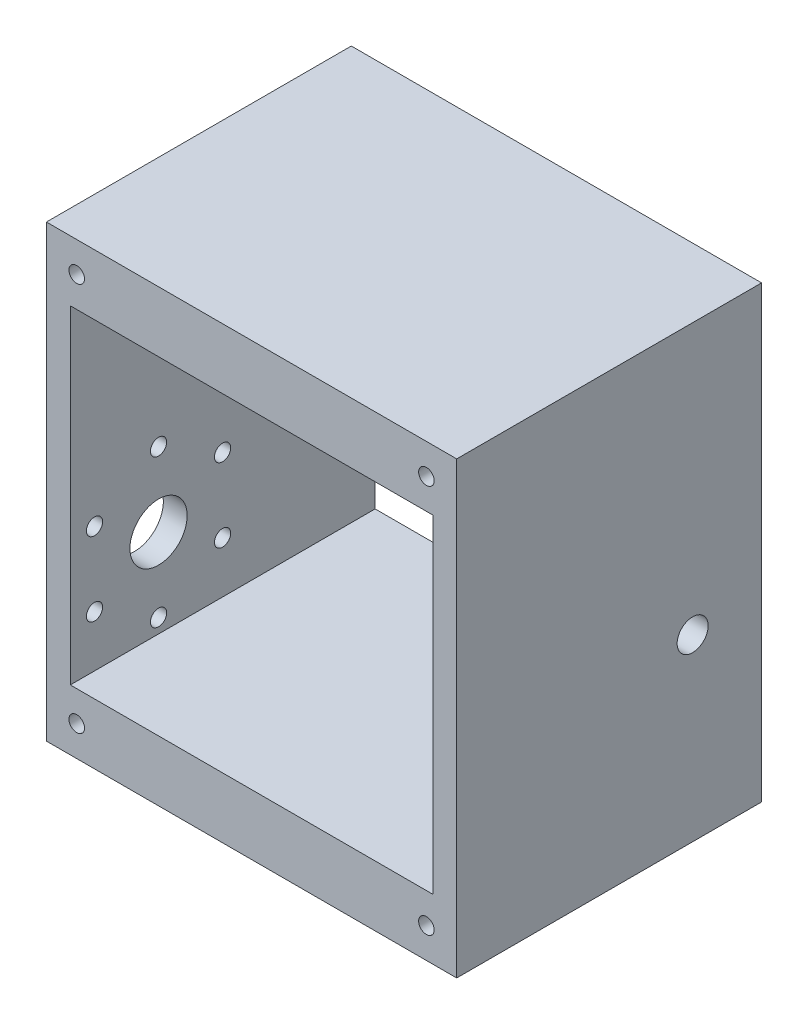
SolidWorks part; units mm, degrees
ref_plane "Front Plane" through (0, 0, 0) normal (0, 0, 1) x (1, 0, 0)
ref_plane "Top Plane" through (0, 0, 0) normal (0, 1, 0) x (1, 0, 0)
ref_plane "Right Plane" through (0, 0, 0) normal (1, 0, 0) x (0, 0, -1)
sketch "Sketch1" plane through (0, 0, 0) normal (0, 0, 1) x (1, 0, 0)
  line L1 (-43, -47.117) -> (43, -47.117)
  line L2 (-43, -47.117) -> (-43, 47.117)
  line L3 (-43, 47.117) -> (43, 47.117)
  line L4 (43, -47.117) -> (43, 47.117)
  line L5 (-43, -47.117) -> (43, 47.117) construction
  line L6 (-43, 47.117) -> (43, -47.117) construction
  point P0 (0, 0)
  dimension "D1" = 86
  dimension "D2" = 94.234
extrude "Boss-Extrude1" add sketch "Sketch1" along normal blind 63.9031
sketch "Sketch2" plane through (0, 0, 63.9031) normal (0, 0, 1) x (1, 0, 0)
  line L0 (-43, 47.117) -> (-43, -47.117) construction
  line L1 (-38, -34.417) -> (38, -34.417)
  line L2 (-38, -34.417) -> (-38, 34.417)
  line L3 (-38, 34.417) -> (38, 34.417)
  line L4 (38, -34.417) -> (38, 34.417)
  line L5 (-38, -34.417) -> (38, 34.417) construction
  line L6 (-38, 34.417) -> (38, -34.417) construction
  line L7 (43, 47.117) -> (-43, 47.117) construction
  point P0 (0, 0)
  dimension "D1" = 5
  dimension "D2" = 12.7
extrude "Cut-Extrude1" cut sketch "Sketch2" against normal through all
hole_wizard "Ø6.5 (6.5) Diameter Hole1" positions "Sketch3" profile "Sketch4" hole size "Ø6.5" standard "ANSI Metric" end condition up to next
sketch "Sketch3" plane through (43, 0, 0) normal (1, 0, 0) x (0, 0, -1)
  line L0 (0, -47.117) -> (0, 47.117) construction
  line L1 (0, 34.417) -> (-63.9031, 34.417) construction
  point P0 (-14.4502, -9.525)
  dimension "D1" = 14.4502
  dimension "D2" = 43.942
sketch "Sketch4" plane through (43, -9.525, 14.4502) normal (0, 1, 0) x (0, 0, -1)
  line L0 (0, 0) -> (0, 5)
  line L1 (0, 5) -> (3.25, 5)
  line L2 (3.25, 5) -> (3.25, 0)
  line L5 (3.25, 0) -> (0, 0)
  line L11 (0, -6.35) -> (0, 107.95) construction
  dimension "Thru Hole Dia." = 6.5
  dimension "Thru Hole Depth" = 5
sketch "Sketch5" plane through (-43, 0, 0) normal (-1, 0, 0) x (0, 0, 1)
  line L0 (63.9031, 47.117) -> (63.9031, -47.117) construction
  line L1 (0, -34.417) -> (63.9031, -34.417) construction
  point P0 (45.4031, -15.917)
  dimension "D1" = 18.5
  dimension "D2" = 18.5
hole_wizard "Ø12.0 (12) Diameter Hole1" positions "Sketch6" profile "Sketch7" hole size "Ø12.0" standard "ANSI Metric" end condition up to next
sketch "Sketch6" plane through (-43, 0, 0) normal (-1, 0, 0) x (0, 0, 1)
  point P0 (45.4031, -15.917)
sketch "Sketch7" plane through (-43, -15.917, 45.4031) normal (0, 1, 0) x (0, 0, 1)
  line L0 (0, 0) -> (0, 5)
  line L1 (0, 5) -> (6, 5)
  line L2 (6, 5) -> (6, 0)
  line L5 (6, 0) -> (0, 0)
  line L11 (0, -6.35) -> (0, 107.95) construction
  dimension "Thru Hole Dia." = 12
  dimension "Thru Hole Depth" = 5
hole_wizard "CSK for M3 Flat Head Machine Screw1" positions "Sketch8" profile "Sketch9" countersink size "M3" standard "ANSI Metric" end condition up to next
sketch "Sketch8" plane through (-43, 0, 0) normal (-1, 0, 0) x (0, 0, 1)
  line L0 (45.4031, -15.917) -> (45.4031, -0.417) construction
  point P0 (45.4031, -0.417)
  point P12 (58.8265, -8.167)
  point P13 (58.8265, -23.667)
  point P14 (45.4031, -31.417)
  point P15 (31.9797, -23.667)
  point P16 (31.9797, -8.167)
  dimension "D2" = 15.5
sketch "Sketch9" plane through (-43, -0.417, 45.4031) normal (0, 1, 0) x (0, 0, 1)
  line L0 (0, 0) -> (0, 5)
  line L1 (0, 5) -> (1.7, 5)
  line L2 (1.7, 5) -> (1.7, 1.45)
  line L3 (1.7, 1.45) -> (3.15, 0)
  line L5 (3.15, 0) -> (0, 0)
  line L6 (-1.7, 1.45) -> (-3.15, 0) construction
  line L11 (0, -6.35) -> (0, 107.95) construction
  dimension "Thru Hole Dia." = 3.4
  dimension "Thru Hole Depth" = 5
  dimension "Near C'Sink Dia." = 6.3
  dimension "Near C'Sink Angle" = 90
hole_wizard "#4 Clearance Hole1" positions "Sketch10" profile "Sketch11" hole size "#4" standard "ANSI Inch" end condition through all
sketch "Sketch10" plane through (0, 0, 63.9031) normal (0, 0, 1) x (1, 0, 0)
  line L0 (-43, 47.117) -> (-43, -47.117) construction
  line L1 (43, 47.117) -> (-43, 47.117) construction
  line L2 (43, -47.117) -> (43, 47.117) construction
  line L3 (-43, -47.117) -> (43, -47.117) construction
  point P0 (-36.65, 40.767)
  point P2 (36.65, 40.767)
  point P4 (-36.65, -40.767)
  point P6 (36.65, -40.767)
  dimension "D1" = 6.35
  dimension "D2" = 6.35
  dimension "D3" = 6.35
  dimension "D4" = 6.35
sketch "Sketch11" plane through (-36.65, 40.767, 63.9031) normal (1, 0, 0) x (0, -1, 0)
  line L0 (0, 0) -> (0, 63.9031)
  line L1 (0, 63.9031) -> (1.6319, 63.9031)
  line L2 (1.6319, 63.9031) -> (1.6319, 0)
  line L5 (1.6319, 0) -> (0, 0)
  line L11 (0, -6.35) -> (0, 107.95) construction
  dimension "Thru Hole Dia." = 3.2639
  dimension "Thru Hole Depth" = 63.9031
equation "\"PCB Width\"= 1940mil"
equation "\"PCB Height\"= 2210mil"
equation "\"PCB Thickness\"= 63mil"
equation "\"PCB Mount Height\"= 0.25in"
equation "\"Motor Body Front Diameter\"= 37mm"
equation "\"Motor Body Front Length\"= 30mm"
equation "\"Motor Bearing Length\"= 5mm"
equation "\"Motor Body Back Length\"= 33.3mm"
equation "\"Motor PCR\"= 31mm / 2"
equation "\"Large PVC Fittings Wall Thickness\"= 15in / 64"
equation "\"Large PVC Pipe Outer Diameter\"= 3.5in"
equation "\"Box Width\"= 2 * \"Motor Bearing Length\" + \"Motor Body Front Length\" + \"Motor Body Back Length\" + 0.5in"
equation "\"Box Hole Center to Edge Distance\"= 250mil"
equation "\"Box Ceiling and Floor Thickness\"= 2 * \"Box Hole Center to Edge Distance\""
equation "\"Box Height\"= 2 * \"Box Ceiling and Floor Thickness\" + \"PCB Height\" + 0.5in"
equation "\"Box Middle Depth\"= \"Large PVC Fittings Wall Thickness\" + \"Large PVC Pipe Outer Diameter\" / 2 + \"Motor Body Front Diameter\" / 2 - \"Motor Bearing Length\""
equation "\"D1@Sketch1\"=\"Box Width\""
equation "\"D2@Sketch1\"=\"Box Height\""
equation "\"D1@Boss-Extrude1\"=\"Box Middle Depth\" "
equation "\"D1@Sketch2\"=\"Motor Bearing Length\""
equation "\"D2@Sketch2\"=\"Box Ceiling and Floor Thickness\""
equation "\"D1@Sketch3\"=\"PCB Mount Height\" + \"PCB Thickness\" + 6.5mm"
equation "\"D2@Sketch3\"=\"PCB Height\" - 0.48in"
equation "\"Motor Body Front Radius\"= \"Motor Body Front Diameter\" / 2"
equation "\"D1@Sketch5\"=\"Motor Body Front Radius\""
equation "\"D2@Sketch5\"=\"Motor Body Front Radius\""
equation "\"D2@Sketch8\"=\"Motor PCR\""
equation "\"D1@Sketch10\"=\"Box Hole Center to Edge Distance\""
equation "\"D2@Sketch10\"=\"Box Hole Center to Edge Distance\""
equation "\"D3@Sketch10\"=\"Box Hole Center to Edge Distance\""
equation "\"D4@Sketch10\"=\"Box Hole Center to Edge Distance\""
